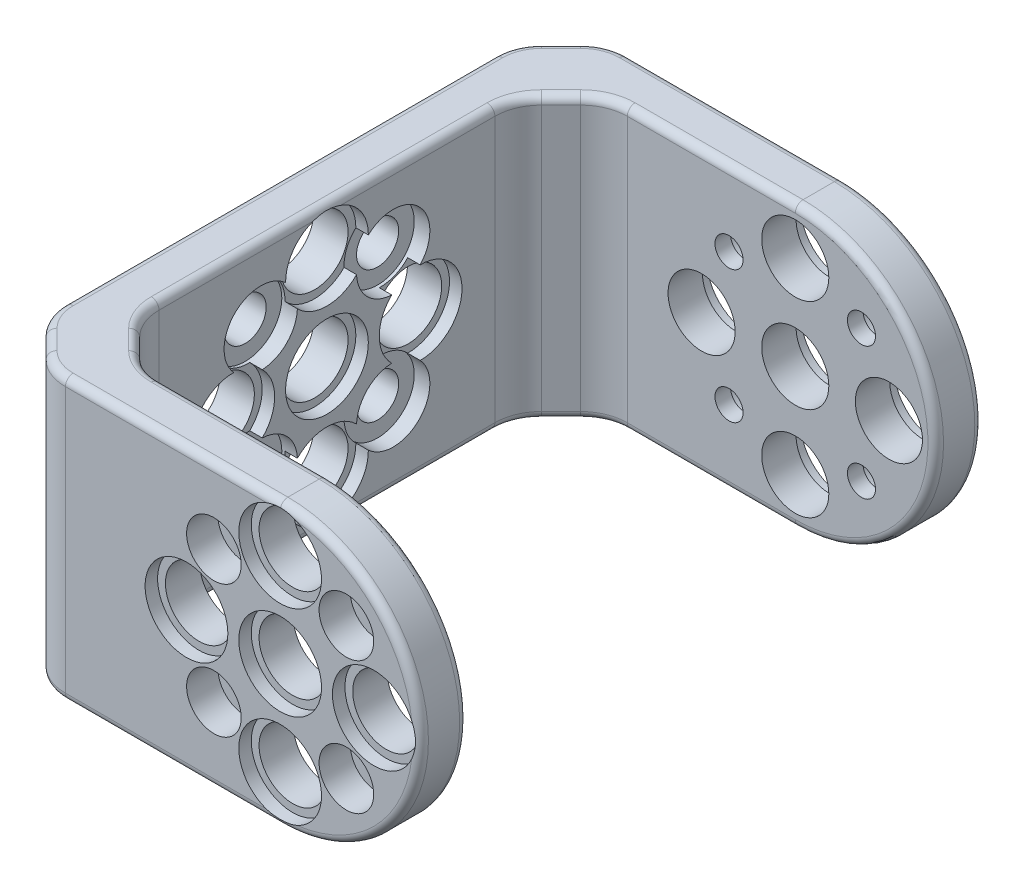
SolidWorks part; units mm, degrees
material "ABS"
ref_plane "Front Plane" through (0, 0, 0) normal (0, 0, 1) x (1, 0, 0)
ref_plane "Top Plane" through (0, 0, 0) normal (0, 1, 0) x (1, 0, 0)
ref_plane "Right Plane" through (0, 0, 0) normal (1, 0, 0) x (0, 0, -1)
sketch "Sketch1" plane through (0, 0, 0) normal (0, 0, 1) x (1, 0, 0)
  circle A0 centre (0, 0) radius 9 construction
  point P3 (0, 6)
  point P6 (4.2426, 4.2426)
  point P7 (6, 0)
  point P8 (4.2426, -4.2426)
  point P9 (0, -6)
  point P10 (-4.2426, -4.2426)
  point P11 (-6, 0)
  point P12 (-4.2426, 4.2426)
  point P13 (0, 0)
  dimension "D1" = 18
  dimension "D2" = 6
  dimension "D3" = 8
sketch "Sketch2" plane through (0, 0, 0) normal (0, 0, 1) x (1, 0, 0)
  line L0 (-18, 9) -> (-18, -9) construction
  line L1 (-18, 0) -> (-27.7608, 0) construction
  dimension "D1" = 18
  dimension "D2" = 18
sketch "Sketch8" plane through (0, 0, 0) normal (1, 0, 0) x (0, 0, -1)
  circle A0 centre (0, 0) radius 9 construction
  point P3 (0, 6)
  point P8 (4.2426, 4.2426)
  point P9 (6, 0)
  point P10 (4.2426, -4.2426)
  point P11 (0, -6)
  point P12 (-4.2426, -4.2426)
  point P13 (-6, 0)
  point P14 (-4.2426, 4.2426)
  point P15 (0, 0)
  dimension "D2" = 18
  dimension "D3" = 6
  dimension "D1" = 8
sketch "Sketch3" plane through (0, 0, 0) normal (0, 0, 1) x (1, 0, 0)
  line L0 (-18, 9) -> (-18, -9) construction
  line L1 (-18, 9) -> (-18, -9)
  line L2 (-18, 9) -> (0, 9)
  line L3 (0, -9) -> (-18, -9)
  circle A0 centre (0, 0) radius 9 construction
  arc A1 (0, -9) -> (0, 9) centre (0, 0) ccw
extrude "Boss-Extrude1" add sketch "Sketch3" along normal blind 18
shell "Shell1" thickness 3 removed face at (-6.75, 0, 0) removed face at (-9, -9, 9) removed face at (-9, 9, 9) removed face at (4.5, 0, 9)
hole_wizard "CBORE for  Hex Socket Head Cap Screw1" positions "Sketch5" profile "Sketch4" counterbore size "M1.6" standard "ISO" end condition through all
sketch "Sketch5" plane through (0, 0, 18) normal (0, 0, 1) x (1, 0, 0)
  point P0 (-4.2426, 4.2426)
  point P3 (4.2426, 4.2426)
  point P6 (4.2426, -4.2426)
  point P9 (-4.2426, -4.2426)
sketch "Sketch4" plane through (-4.2426, 4.2426, 18) normal (1, 0, 0) x (0, -1, 0)
  line L0 (0, 0) -> (0, 18)
  line L1 (0, 18) -> (0.9, 18)
  line L3 (0.9, 18) -> (0.9, 2)
  line L4 (0.9, 2) -> (1.75, 2)
  line L5 (1.75, 2) -> (1.75, 0)
  line L7 (1.75, 0) -> (0, 0)
  line L11 (0, -6.35) -> (0, 107.95) construction
  dimension "Thru Hole Dia." = 1.8
  dimension "Thru Hole Depth" = 18
  dimension "C'Bore Dia." = 3.5
  dimension "C'Bore Depth" = 2
hole_wizard "Hole1" positions "Sketch7" profile "Sketch6" legacy end condition through all
sketch "Sketch7" plane through (0, 0, 18) normal (0, 0, 1) x (1, 0, 0)
  point P0 (0, 6)
  point P3 (0, 0)
  point P6 (-6, 0)
  point P9 (0, -6)
  point P12 (6, 0)
sketch "Sketch6" plane through (0, 6, 18) normal (1, 0, 0) x (0, -1, 0)
  line L0 (0, 0) -> (0, 18)
  line L1 (0, 18) -> (2.15, 18)
  line L2 (2.15, 18) -> (2.15, 0.8)
  line L3 (2.15, 0.8) -> (2.65, 0.8)
  line L4 (2.65, 0.8) -> (2.65, 0)
  line L5 (2.65, 0) -> (0, 0)
  line L6 (0, 110) -> (0, -10) construction
  dimension "Diameter" = 4.3
  dimension "Depth" = 18
  dimension "C-Bore Diameter" = 5.3
  dimension "C-Bore Depth" = 0.8
hole_wizard "Hole2" positions "Sketch10" profile "Sketch9" legacy
sketch "Sketch10" plane through (-15, 0, 0) normal (1, 0, 0) x (0, 0, -1)
  point P0 (0, 6)
  point P3 (0, 0)
  point P6 (0, -6)
  point P9 (-6, 0)
sketch "Sketch9" plane through (-15, 6, 0) normal (0, 1, 0) x (0, 0, -1)
  line L0 (0, 0) -> (0, 15)
  line L1 (0, 15) -> (2.15, 15)
  line L2 (2.15, 15) -> (2.15, 0.8)
  line L3 (2.15, 0.8) -> (2.65, 0.8)
  line L4 (2.65, 0.8) -> (2.65, 0)
  line L5 (2.65, 0) -> (0, 0)
  line L6 (0, 110) -> (0, -10) construction
  dimension "Diameter" = 4.3
  dimension "Depth" = 15
  dimension "C-Bore Diameter" = 5.3
  dimension "C-Bore Depth" = 0.8
hole_wizard "CBORE for M2 Hex Socket Head Cap Screw2" positions "Sketch12" profile "Sketch11" counterbore size "M2" standard "ISO" end condition through all
sketch "Sketch12" plane through (-15, 0, 0) normal (1, 0, 0) x (0, 0, -1)
  point P0 (-4.2426, 4.2426)
  point P3 (-4.2426, -4.2426)
sketch "Sketch11" plane through (-15, 4.2426, 4.2426) normal (0, 1, 0) x (0, 0, -1)
  line L0 (0, 0) -> (0, 3)
  line L1 (0, 3) -> (1.35, 3)
  line L3 (1.35, 3) -> (1.35, 1)
  line L4 (1.35, 1) -> (2.35, 1)
  line L5 (2.35, 1) -> (2.35, 0)
  line L7 (2.35, 0) -> (0, 0)
  line L11 (0, -6.35) -> (0, 107.95) construction
  dimension "Thru Hole Dia." = 2.7
  dimension "Thru Hole Depth" = 3
  dimension "C'Bore Dia." = 4.7
  dimension "C'Bore Depth" = 1
chamfer "Chamfer1" distance 3 angle 45 2 edges at (-15, 0, 15) (-18, 0, 18)
fillet "Fillet1" radius 3 4 edges at (-12, 0, 15) (-15, 0, 12) (-18, 0, 15) (-15, 0, 18)
fillet "Fillet2" radius 0.5 22 edges at (-15, -9, 5.3787) (-14.7716, -9, 11.9054) (-13.5, -9, 13.5) (-11.9054, -9, 14.7716) (-5.3787, -9, 15) (9, 0, 15) (-5.3787, 9, 15) (-11.9054, 9, 14.7716) (-13.5, 9, 13.5) (-14.7716, 9, 11.9054) (-18, -9, 6.8787) (-17.7716, -9, 14.9054) (-16.5, -9, 16.5) (-14.9054, -9, 17.7716) (-6.8787, -9, 18) (9, 0, 18) (-18, 9, 6.8787) (-17.7716, 9, 14.9054) (-16.5, 9, 16.5) (-14.9054, 9, 17.7716) (-15, 9, 5.3787) (-6.8787, 9, 18)
mirror "Mirror1" about plane through (0, 0, 0) normal (0, 0, 1) of bodies 106 103
